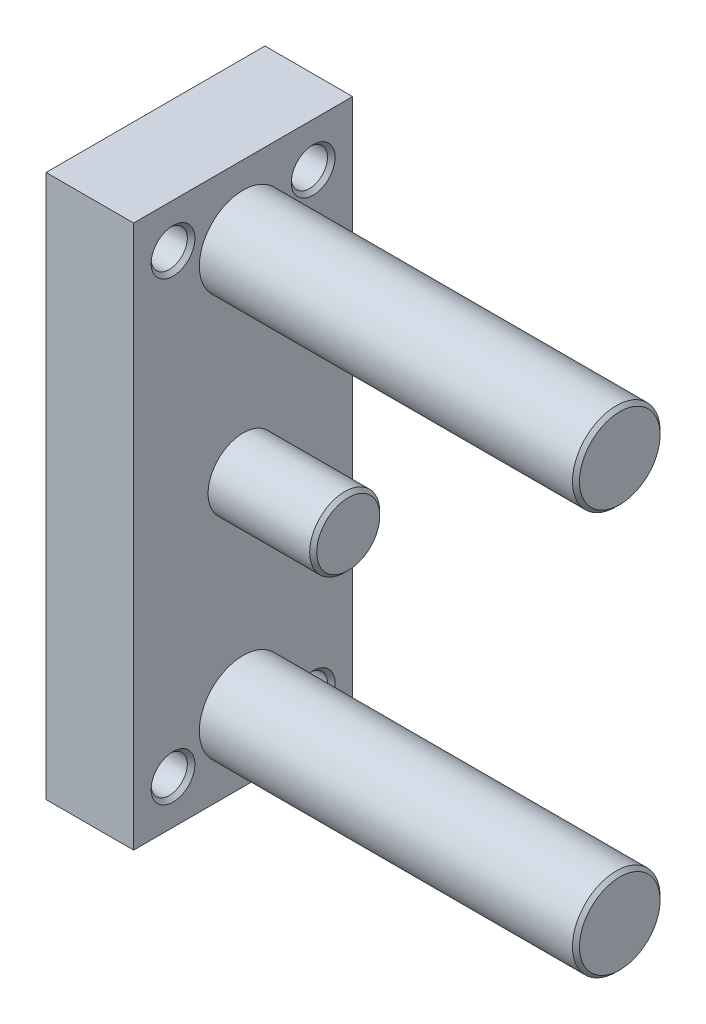
SolidWorks part; units mm, degrees
ref_plane "前视基准面" through (0, 0, 0) normal (0, 0, 1) x (1, 0, 0)
ref_plane "上视基准面" through (0, 0, 0) normal (0, 1, 0) x (1, 0, 0)
ref_plane "右视基准面" through (0, 0, 0) normal (1, 0, 0) x (0, 0, -1)
sketch "草图1" plane through (0, 0, 0) normal (1, 0, 0) x (0, 0, -1)
  line L0 (-12.5, -31) -> (12.5, -31)
  line L1 (12.5, -31) -> (12.5, 31)
  line L2 (12.5, 31) -> (-12.5, 31)
  line L3 (-12.5, 31) -> (-12.5, -31)
extrude "凸台-拉伸1" add sketch "草图1" along normal blind 10
ref_plane "基准面4" through (0, 26, 0) normal (0, 1, 0) x (1, 0, 0)
sketch "草图2" plane through (0, 26, 0) normal (0, 1, 0) x (1, 0, 0)
  line L0 (0, 8) -> (0, 10.5)
  line L1 (0, 10.5) -> (0.433, 10.067)
  line L2 (0.433, 10.067) -> (9.567, 10.067)
  line L3 (9.567, 10.067) -> (10, 10.5)
  line L4 (10, 10.5) -> (10, 8)
  line L5 (10, 8) -> (0, 8)
  line L6 (10, 8) -> (0, 8) construction
revolve "切除-旋转1" cut sketch "草图2" angle 360 about L6 reverse direction yes
cosmetic thread "装饰螺纹线1" parameters "D1"=10, "D2"=5
sketch "草图3" plane through (0, 0, 0) normal (1, 0, 0) x (0, 0, -1)
  line L0 (8, 26) -> (-992, 26)
  line L1 (8, 26) -> (8, -974)
pattern_linear "阵列(线性)1" count 2 spacing 16 along (0, 0, 1) count 2 spacing 52 along (0, -1, 0) of "切除-旋转1"
ref_plane "基准面5" through (0, 23, 0) normal (0, 1, 0) x (1, 0, 0)
sketch "草图4" plane through (0, 23, 0) normal (0, 1, 0) x (1, 0, 0)
  line L0 (0, 0) -> (0, 3.8)
  line L1 (0, 3.8) -> (5.5556, 3.8)
  line L2 (5.5556, 3.8) -> (5.5556, 3.5)
  line L3 (5.5556, 3.5) -> (2.0556, 3.5)
  line L4 (2.0556, 3.5) -> (1.5556, 3)
  line L5 (1.5556, 3) -> (1.5556, 1.5)
  line L6 (1.5556, 1.5) -> (4.1556, 1.5)
  line L7 (4.1556, 1.5) -> (5.0216, 0)
  line L8 (5.0216, 0) -> (0, 0)
  line L9 (5.0216, 0) -> (0, 0) construction
revolve "切除-旋转2" cut sketch "草图4" angle 360 about L9 reverse direction yes
sketch "草图5" plane through (0, 0, 0) normal (0, 1, 0) x (1, 0, 0)
  line L0 (0, 0) -> (0, 3.8)
  line L1 (0, 3.8) -> (5.5556, 3.8)
  line L2 (5.5556, 3.8) -> (5.5556, 3.5)
  line L3 (5.5556, 3.5) -> (2.0556, 3.5)
  line L4 (2.0556, 3.5) -> (1.5556, 3)
  line L5 (1.5556, 3) -> (1.5556, 1.5)
  line L6 (1.5556, 1.5) -> (4.1556, 1.5)
  line L7 (4.1556, 1.5) -> (5.0216, 0)
  line L8 (5.0216, 0) -> (0, 0)
  line L9 (5.0216, 0) -> (0, 0) construction
revolve "切除-旋转3" cut sketch "草图5" angle 360 about L9 reverse direction yes
ref_plane "基准面6" through (0, -23, 0) normal (0, 1, 0) x (1, 0, 0)
sketch "草图6" plane through (0, -23, 0) normal (0, 1, 0) x (1, 0, 0)
  line L0 (0, 0) -> (0, 3.8)
  line L1 (0, 3.8) -> (5.5556, 3.8)
  line L2 (5.5556, 3.8) -> (5.5556, 3.5)
  line L3 (5.5556, 3.5) -> (2.0556, 3.5)
  line L4 (2.0556, 3.5) -> (1.5556, 3)
  line L5 (1.5556, 3) -> (1.5556, 1.5)
  line L6 (1.5556, 1.5) -> (4.1556, 1.5)
  line L7 (4.1556, 1.5) -> (5.0216, 0)
  line L8 (5.0216, 0) -> (0, 0)
  line L9 (5.0216, 0) -> (0, 0) construction
revolve "切除-旋转4" cut sketch "草图6" angle 360 about L9 reverse direction yes
sketch "草图7" plane through (0, 0, 0) normal (0, 1, 0) x (1, 0, 0)
  line L0 (10, 0) -> (10, 4)
  line L1 (10, 4) -> (21.6, 4)
  line L2 (21.6, 4) -> (22, 3.6)
  line L3 (22, 3.6) -> (22, 0)
  line L4 (22, 0) -> (10, 0)
  line L5 (22, 0) -> (10, 0) construction
revolve "旋转1" add sketch "草图7" angle 360 about L5 reverse direction yes
ref_plane "基准面7" through (0, -23, 0) normal (0, 1, 0) x (1, 0, 0)
sketch "草图8" plane through (0, -23, 0) normal (0, 1, 0) x (1, 0, 0)
  line L0 (10, 0) -> (10, 5)
  line L1 (10, 5) -> (52.6, 5)
  line L2 (52.6, 5) -> (53, 4.6)
  line L3 (53, 4.6) -> (53, 0)
  line L4 (53, 0) -> (10, 0)
  line L5 (53, 0) -> (10, 0) construction
revolve "旋转2" add sketch "草图8" angle 360 about L5 reverse direction yes
ref_plane "基准面8" through (0, 23, 0) normal (0, 1, 0) x (1, 0, 0)
sketch "草图9" plane through (0, 23, 0) normal (0, 1, 0) x (1, 0, 0)
  line L0 (10, 0) -> (10, 5)
  line L1 (10, 5) -> (52.6, 5)
  line L2 (52.6, 5) -> (53, 4.6)
  line L3 (53, 4.6) -> (53, 0)
  line L4 (53, 0) -> (10, 0)
  line L5 (53, 0) -> (10, 0) construction
revolve "旋转3" add sketch "草图9" angle 360 about L5 reverse direction yes
ref_plane "基准面9" through (12, 0, 0) normal (1, 0, 0) x (0, 0, -1)
ref_plane "s XY" through (12, 0, 0) normal (1, 0, 0) x (0, 0, -1)
ref_plane "s XZ" through (0, 0, 0) normal (0, -1, 0) x (-1, 0, 0)
ref_plane "s YZ" through (0, 0, 0) normal (0, 0, -1) x (-1, 0, 0)
ref_axis "s X" through (12, 0, 80.9) along (0, 0, -1)
ref_axis "s Y" through (12, -50, 0) along (0, 1, 0)
ref_axis "s Z" through (80.9, 0, 0) along (-1, 0, 0)
sketch3d "s"
  point P0 (12, 0, 0)
